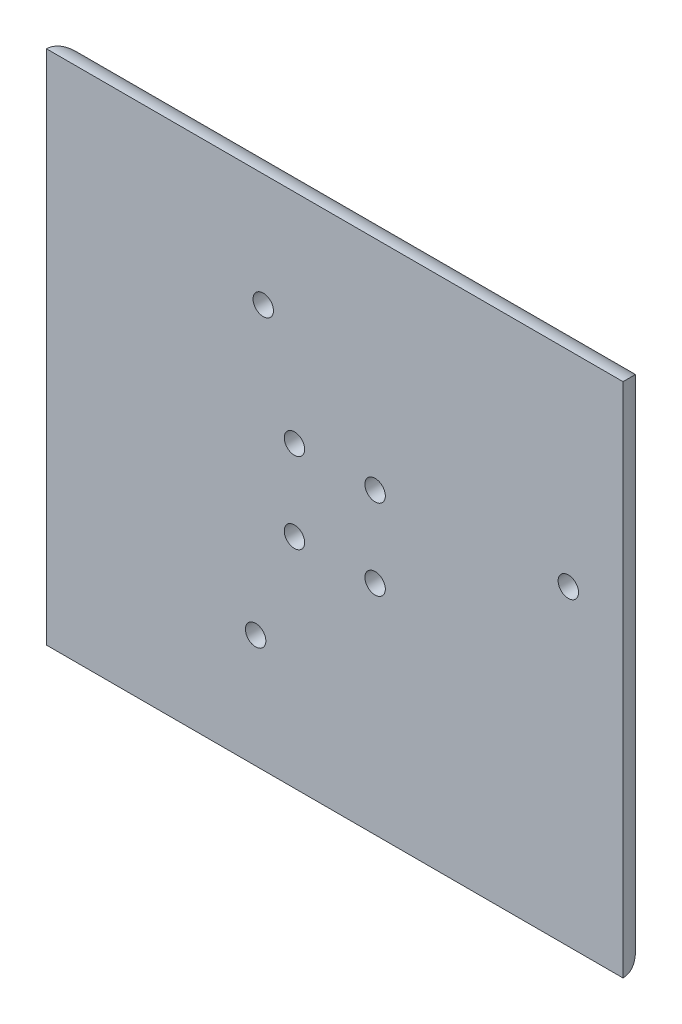
SolidWorks part; units mm, degrees
ref_plane "Plan de face" through (0, 0, 0) normal (0, 0, 1) x (1, 0, 0)
ref_plane "Plan de dessus" through (0, 0, 0) normal (0, 1, 0) x (1, 0, 0)
ref_plane "Plan de droite" through (0, 0, 0) normal (1, 0, 0) x (0, 0, -1)
sketch "Esquisse1" plane through (0, 0, 0) normal (0, 0, 1) x (1, 0, 0)
  line L1 (50.2, -56.1595) -> (-45.8, -56.1595)
  line L2 (50.2, -56.1595) -> (50.2, 29.8405)
  line L3 (50.2, 29.8405) -> (-45.8, 29.8405)
  line L4 (-45.8, -56.1595) -> (-45.8, 29.8405)
  point P0 (0, 0)
  dimension "D1" = 96
  dimension "D2" = 86
extrude "Boss.-Extru.1" add sketch "Esquisse1" along normal blind 5
sketch "trou_support_moteur" plane through (0, 0, 5) normal (0, 0, 1) x (1, 0, 0)
  circle A0 centre (2.2, -13.1595) radius 9.5 construction
  dimension "D1" = 19
sketch "Esquisse33" plane through (0, 0, 5) normal (0, 0, 1) x (1, 0, 0)
  line L1 (-4.5175, -6.4419) -> (8.9175, -6.4419) construction
  line L2 (-4.5175, -6.4419) -> (-4.5175, -19.877) construction
  line L3 (-4.5175, -19.877) -> (8.9175, -19.877) construction
  line L4 (8.9175, -6.4419) -> (8.9175, -19.877) construction
  line L5 (-4.5175, -6.4419) -> (8.9175, -19.877) construction
  line L6 (-4.5175, -19.877) -> (8.9175, -6.4419) construction
  circle A0 centre (2.2, -13.1595) radius 9.5 construction
  point P0 (2.2, -13.1595)
fillet "Congé2" radius 5 4 edges at (-45.8, -13.1595, 0) (2.2, -56.1595, 0) (50.2, -13.1595, 0) (2.2, 29.8405, 0)
sketch "EsquisseEntretoise1" plane through (0, 0, 5) normal (0, 0, 1) x (1, 0, 0)
  line L0 (50.2, 29.8405) -> (-45.8, 29.8405) construction
  line L1 (-45.8, 29.8405) -> (-45.8, -56.1595) construction
  circle A0 centre (-9.71, 10.9605) radius 2 construction
  dimension "D1" = 4
  dimension "D2" = 18.88
  dimension "D3" = 36.09
sketch "EsquisseEntretoise2" plane through (0, 0, 5) normal (0, 0, 1) x (1, 0, 0)
  line L0 (-45.8, -56.1595) -> (50.2, -56.1595) construction
  line L2 (-45.8, 29.8405) -> (-45.8, -56.1595) construction
  circle A0 centre (-10.98, -37.2995) radius 2 construction
  dimension "D1" = 4
  dimension "D2" = 18.86
  dimension "D3" = 34.82
sketch "EsquisseEntretoise3" plane through (0, 0, 5) normal (0, 0, 1) x (1, 0, 0)
  line L0 (50.2, -56.1595) -> (50.2, 29.8405) construction
  line L1 (50.2, 29.8405) -> (-45.8, 29.8405) construction
  circle A0 centre (41.09, -4.2795) radius 2 construction
  dimension "D1" = 4
  dimension "D2" = 9.11
  dimension "D3" = 34.12
hole_wizard "TrouM3" positions "Esquisse34" profile "Esquisse35" hole size "M3" standard "ISO" end condition up to next
sketch "Esquisse34" plane through (0, 0, 5) normal (0, 0, 1) x (1, 0, 0)
  point P0 (-9.71, 10.9605)
  point P3 (41.09, -4.2795)
  point P6 (-10.98, -37.2995)
  point P9 (-4.5175, -19.877)
  point P12 (-4.5175, -6.4419)
  point P15 (8.9175, -6.4419)
  point P18 (8.9175, -19.877)
sketch "Esquisse35" plane through (-9.71, 10.9605, 5) normal (1, 0, 0) x (0, -1, 0)
  line L0 (0, 0) -> (0, 5)
  line L1 (0, 5) -> (1.7, 5)
  line L2 (1.7, 5) -> (1.7, 0)
  line L5 (1.7, 0) -> (0, 0)
  line L11 (0, -6.35) -> (0, 107.95) construction
  dimension "Diamètre du perçage jusqu'au prochain" = 3.4
  dimension "Profondeur du perçage jusqu'au prochain" = 5
